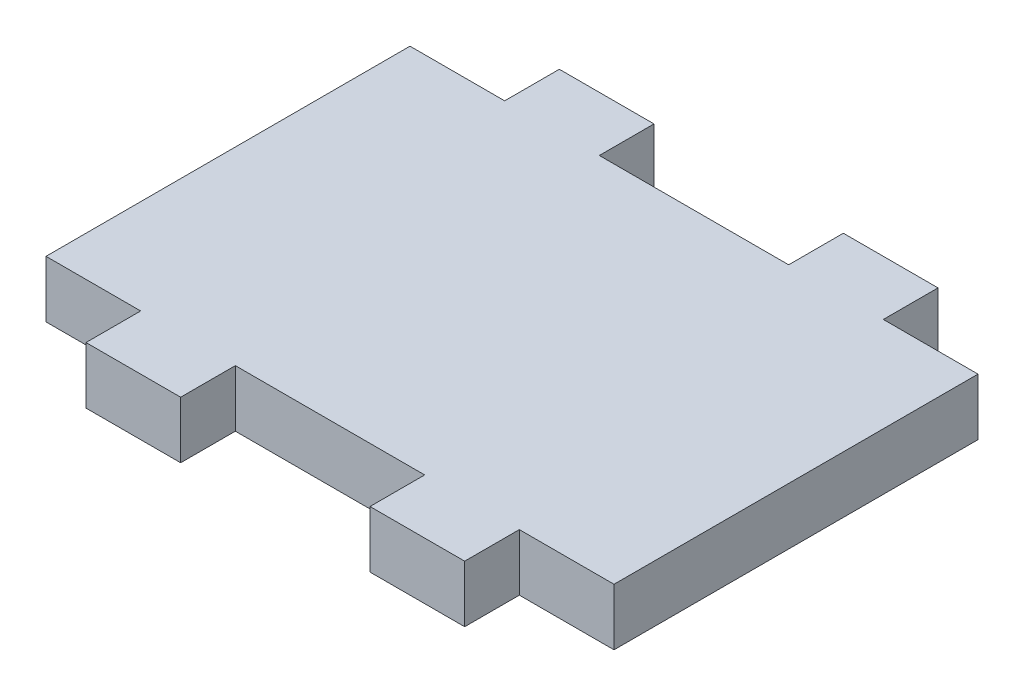
SolidWorks part; units mm, degrees
ref_plane "Front Plane" through (0, 0, 0) normal (0, 0, 1) x (1, 0, 0)
ref_plane "Top Plane" through (0, 0, 0) normal (0, 1, 0) x (1, 0, 0)
ref_plane "Right Plane" through (0, 0, 0) normal (1, 0, 0) x (0, 0, -1)
sketch "Sketch1" plane through (0, 0, 0) normal (0, 1, 0) x (1, 0, 0)
  line L0 (-25, 25) -> (-25, -25)
  line L1 (-35, 25) -> (35, 25)
  line L2 (-35, 25) -> (-35, -25)
  line L3 (-35, -25) -> (35, -25)
  line L4 (35, 25) -> (35, -25)
  line L5 (-35, 25) -> (35, -25) construction
  line L6 (-35, -25) -> (35, 25) construction
  point P0 (0, 0)
  dimension "D2" = 50
  dimension "D1" = 70
  dimension "D3" = 10
sketch "Sketch2" plane through (0, 0, 0) normal (0, 0, 1) x (1, 0, 0)
  line L0 (0, 0) -> (0, 6) construction
  line L1 (-35, 0) -> (35, 0) construction
  dimension "D1" = 6
extrude "Boss-Extrude1" add sketch "Sketch1" along normal up to vertex (6 mm away) contours L4 L1 L0 L3 region at (5, 0, 0) up to point (0, 6, 0)
sketch "Sketch3" plane through (0, 6, 0) normal (0, 1, 0) x (1, 0, 0)
  line L0 (-25, 25) -> (35, 25) construction
  line L1 (35, 25) -> (25, 25)
  line L2 (35, 25) -> (35, 19.2244)
  line L3 (35, 19.2244) -> (25, 19.2244)
  line L4 (25, 25) -> (25, 19.2244)
  line L5 (25, 19.2244) -> (15, 19.2244) construction
  line L6 (25, 19.2244) -> (25, 25) construction
  line L7 (25, 25) -> (15, 25) construction
  line L8 (15, 19.2244) -> (15, 25) construction
  line L10 (15, 25) -> (-5, 25)
  line L11 (15, 25) -> (15, 19.2244)
  line L12 (15, 19.2244) -> (-5, 19.2244)
  line L13 (-5, 25) -> (-5, 19.2244)
  line L18 (-5, 19.2244) -> (-15, 19.2244) construction
  line L19 (-5, 19.2244) -> (-5, 25) construction
  line L20 (-5, 25) -> (-15, 25) construction
  line L21 (-15, 19.2244) -> (-15, 25) construction
  line L22 (-25, 25) -> (-15, 25)
  line L23 (-25, 25) -> (-25, 19.2244)
  line L24 (-25, 19.2244) -> (-15, 19.2244)
  line L25 (-15, 25) -> (-15, 19.2244)
  point P15 (-15, 19.2244)
  dimension "D1" = 10
  dimension "D2" = 20
  dimension "D3" = 5.7756
extrude "Cut-Extrude2" cut sketch "Sketch3" against normal through all
mirror "Mirror2" about plane through (0, 0, 0) normal (0, 0, 1) of "Cut-Extrude2"
equation "\"glass_width\" = 150"
equation "\"glass_height\"= 100"
equation "\"glass_thickness\"= 4"
equation "\"brood_space\"= 42"
equation "\"t1\"= 6"
equation "\"t2\"= 3.2"
equation "\"box_depth\"= \"brood_space\" + \"glass_thickness\" + \"glass_thickness\" + \"t2\" + \"t2\""
equation "\"box_width\"= \"glass_width\" + \"t1\" + \"t1\""
equation "\"food_height\"= 70"
equation "\"box_height\" = \"glass_height\" + ( \"t1\" * 3 ) + \"food_height\""
equation "\"D1@Sketch2\"=\"t1\""
equation "\"D2@Sketch1\"=\"glass_thickness\"+\"glass_thickness\"+\"brood_space\""
equation "\"D1@Sketch1\"=\"food_height\""
